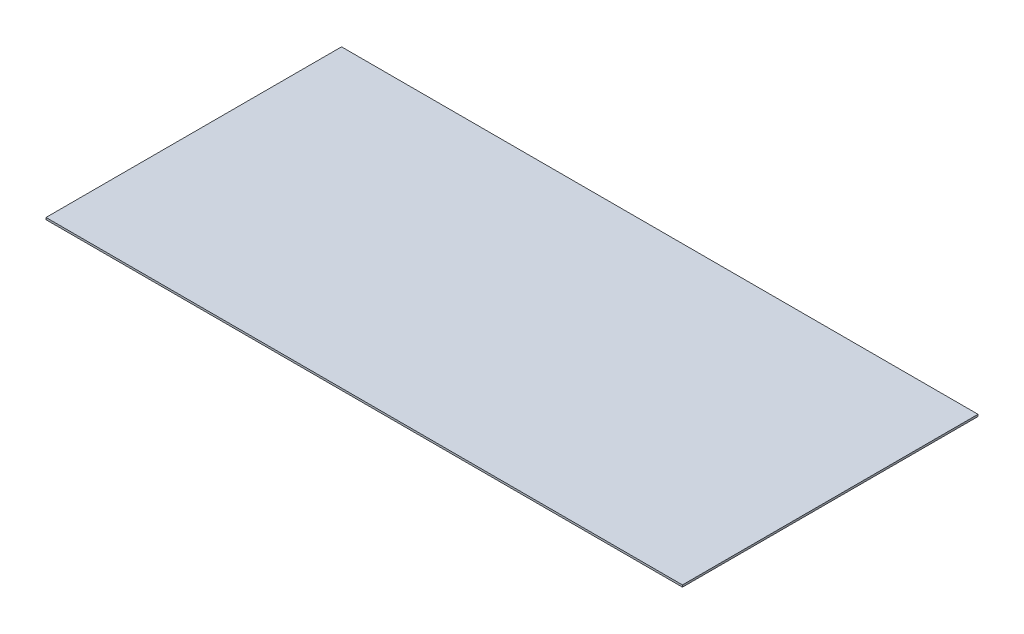
SolidWorks part; units mm, degrees
ref_plane "Front Plane" through (0, 0, 0) normal (0, 0, 1) x (1, 0, 0)
ref_plane "Top Plane" through (0, 0, 0) normal (0, 1, 0) x (1, 0, 0)
ref_plane "Right Plane" through (0, 0, 0) normal (1, 0, 0) x (0, 0, -1)
sketch "Sketch1" plane through (0, 0, 0) normal (0, 1, 0) x (1, 0, 0)
  line L1 (-800.1, -368.3) -> (800.1, -368.3)
  line L2 (-800.1, -368.3) -> (-800.1, 368.3)
  line L3 (-800.1, 368.3) -> (800.1, 368.3)
  line L4 (800.1, -368.3) -> (800.1, 368.3)
  line L5 (-800.1, -368.3) -> (800.1, 368.3) construction
  line L6 (-800.1, 368.3) -> (800.1, -368.3) construction
extrude "Boss-Extrude1" add sketch "Sketch1" along normal blind 2.5 and the other way blind 2.5
sketch "Sketch2" plane through (0, 0, 0) normal (0, 1, 0) x (1, 0, 0)
  line L19 (-800.1, 368.3) -> (800.1, 368.3)
  line L20 (-800.1, 368.3) -> (-800.1, -368.3)
  line L21 (-800.1, -368.3) -> (800.1, -368.3)
  line L22 (800.1, 368.3) -> (800.1, -368.3)
  line L23 (806.1, -374.3) -> (-806.1, -374.3)
  line L24 (806.1, -374.3) -> (806.1, 374.3)
  line L25 (806.1, 374.3) -> (-806.1, 374.3)
  line L26 (-806.1, -374.3) -> (-806.1, 374.3)
  dimension "D1" = 6
  dimension "D2" = 6
  dimension "D3" = 6
  dimension "D6" = 6
extrude "Boss-Extrude2" add sketch "Sketch2" along normal up to surface and the other way up to surface up to face at (0, 2.5, 0) other way up to face at (0, -2.5, 0)
